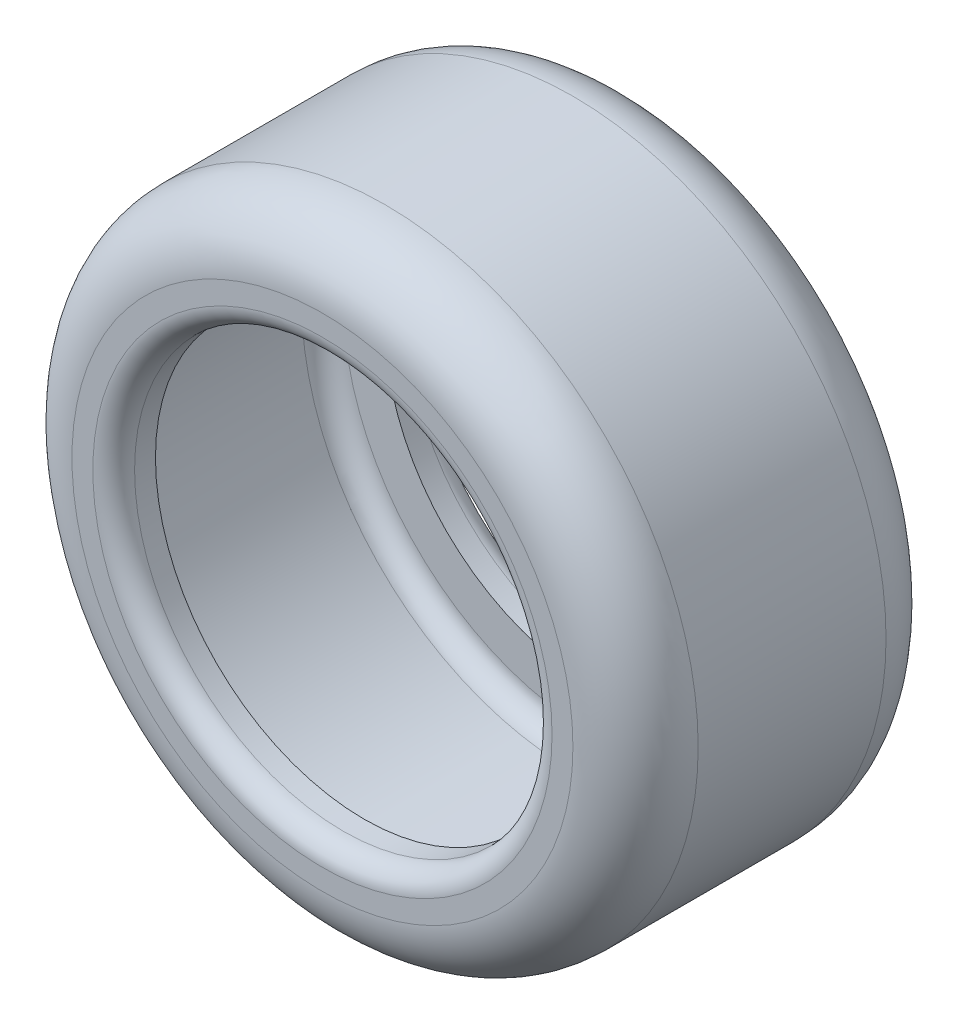
SolidWorks part; units mm, degrees
ref_plane "Front Plane" through (0, 0, 0) normal (0, 0, 1) x (1, 0, 0)
ref_plane "Top Plane" through (0, 0, 0) normal (0, 1, 0) x (1, 0, 0)
ref_plane "Right Plane" through (0, 0, 0) normal (1, 0, 0) x (0, 0, -1)
sketch "Sketch2" plane through (0, 0, 0) normal (0, 0, 1) x (1, 0, 0)
  circle A0 centre (-15.434, 9.0591) radius 25.4
  dimension "D1" = 50.8
extrude "Extrude-Thin1" add sketch "Sketch2" along normal blind 38.1 thin thin type one direction wall 12.7
fillet "Fillet1" radius 7.62 2 edges at (22.666, 9.0591, 0) (22.666, 9.0591, 38.1)
fillet "Fillet2" radius 2.54 2 edges at (9.966, 9.0591, 0) (9.966, 9.0591, 38.1)
shell "Shell1" thickness 5.08 removed face at (9.966, 9.0591, 2.54)
